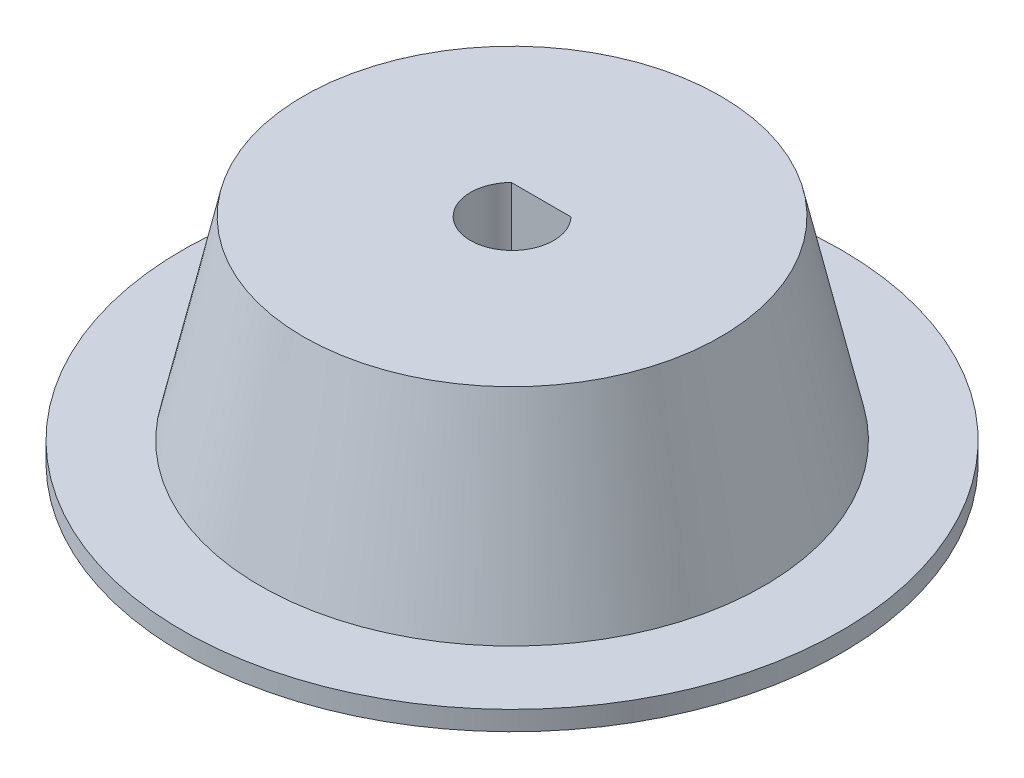
SolidWorks part; units mm, degrees
ref_plane "Front Plane" through (0, 0, 0) normal (0, 0, 1) x (1, 0, 0)
ref_plane "Top Plane" through (0, 0, 0) normal (0, 1, 0) x (1, 0, 0)
ref_plane "Right Plane" through (0, 0, 0) normal (1, 0, 0) x (0, 0, -1)
sketch "Sketch1" plane through (0, 0, 0) normal (0, 1, 0) x (1, 0, 0)
  circle A0 centre (0, 0) radius 13
  dimension "D1" = 26
extrude "Boss-Extrude1" add sketch "Sketch1" along normal blind 10
sketch "Sketch2" plane through (0, 0, 0) normal (1, 0, 0) x (0, 0, -1)
  line L0 (-13, 0) -> (-10.7574, 10)
  line L1 (13, 10) -> (-13, 10) construction
  line L2 (-10.7574, 10) -> (-13, 10)
  line L3 (-13, 10) -> (-13, 0)
  line L4 (0, 0) -> (0, 50000) construction
  line L5 (-13, 0) -> (13, 0) construction
  point P11 (0, 0)
  dimension "D1" = 12.64
revolve "Cut-Revolve1" cut sketch "Sketch2" angle 360 about L4
sketch "Sketch3" plane through (0, 0, 0) normal (0, -1, 0) x (-1, 0, 0)
  circle A0 centre (0, 0) radius 17
  dimension "D1" = 34
extrude "Boss-Extrude2" add sketch "Sketch3" along normal blind 1
sketch "Sketch4" plane through (0, -1, 0) normal (0, -1, 0) x (1, 0, 0)
  line L0 (1.145, -2.3899) -> (1.145, 2.3899)
  line L1 (-1.145, -2.3899) -> (-1.145, 2.3899)
  line L2 (0, 0) -> (35355.3391, 35355.3391) construction
  line L3 (0.8543, 0) -> (50000.8543, 0) construction
  line L4 (-2.3899, 1.145) -> (2.3899, 1.145)
  line L5 (-2.3899, -1.145) -> (2.3899, -1.145)
  circle A0 centre (0, 0) radius 2.65
  dimension "D1" = 5.3
  dimension "D2" = 2.29
  dimension "D3" = 45
extrude "Cut-Extrude1" [suppressed] cut sketch "Sketch4" against normal through all contours L1 L5 L0 L4 | L4 A0 L5 L1 | L0 A0 L1 L4 | L5 A0 L4 L0 | L1 A0 L0 L5
fillet "Fillet1" [suppressed] radius 0.5
sketch "Sketch5" plane through (0, 10, 0) normal (0, 1, 0) x (1, 0, 0)
  line L0 (-1.5403, 1.5) -> (1.5403, 1.5)
  circle A0 centre (0, 0) radius 2.15
  dimension "D1" = 4.3
  dimension "D2" = 1.5
extrude "Cut-Extrude2" cut sketch "Sketch5" against normal through all contours L0 A0 region at (0, 10, 0.1854)
ref_plane "Plane1" through (0, 2.7758, 12.3775) normal (0, 0.2188, 0.9758) x (1, 0, 0)
sketch "Sketch7" plane through (0, 10, 0) normal (0, 1, 0) x (1, 0, 0)
  circle A0 centre (0, -9.7574) radius 1.6
  circle A1 centre (0, 0) radius 9.7574 construction
  circle A2 centre (0, 0) radius 10.7574 construction
  dimension "D1" = 3.2
  dimension "D2" = 1
sketch "Sketch8" plane through (0, 0, 0) normal (0, 1, 0) x (1, 0, 0)
  circle A0 centre (0, -12) radius 1.6
  circle A1 centre (0, 0) radius 12 construction
  circle A2 centre (0, 0) radius 13 construction
  circle A4 centre (0, -9.7574) radius 1.6 construction
  dimension "D1" = 1
loft "Cut-Loft1" [suppressed] cut profiles "Sketch7", "Sketch8"
pattern_circular "CirPattern1" [suppressed] count 15 over 360 of bodies 106
fillet "Fillet2" [suppressed] radius 0.3
